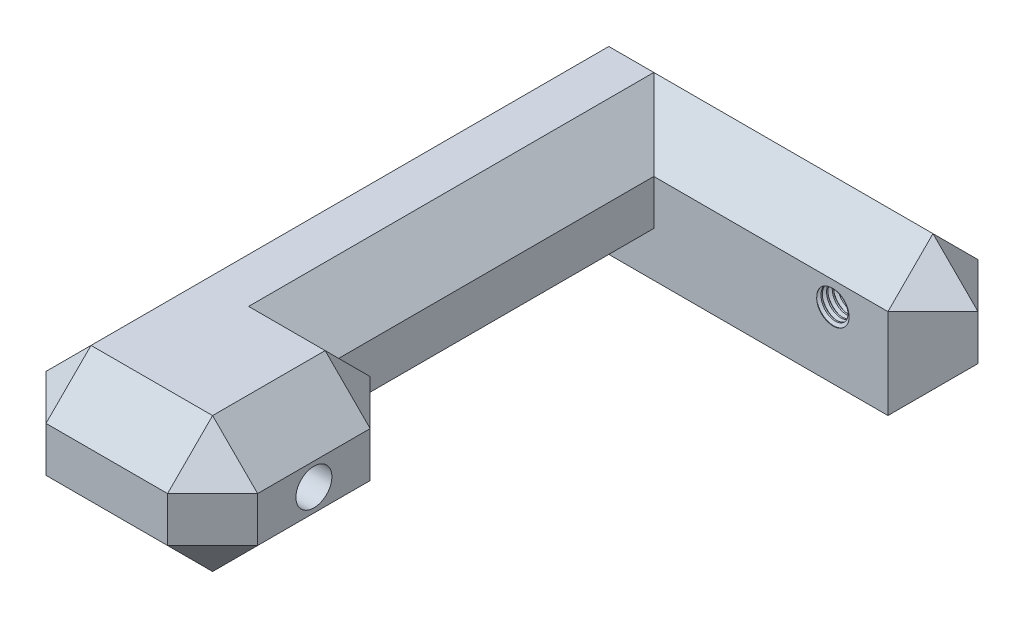
SolidWorks part; units mm, degrees
ref_plane "Front Plane" through (0, 0, 0) normal (0, 0, 1) x (1, 0, 0)
ref_plane "Top Plane" through (0, 0, 0) normal (0, 1, 0) x (1, 0, 0)
ref_plane "Right Plane" through (0, 0, 0) normal (1, 0, 0) x (0, 0, -1)
sketch "Sketch1" plane through (0, 0, 0) normal (0, 1, 0) x (1, 0, 0)
  line L2 (0, 0) -> (0, 45)
  line L3 (0, 45) -> (-17, 45)
  line L5 (0, 0) -> (-47, 0)
  line L6 (-17, 45) -> (-17, 115)
  line L8 (-47, 0) -> (-47, 135)
  line L9 (-47, 135) -> (45, 135)
  line L11 (-17, 115) -> (45, 115)
  line L12 (45, 135) -> (45, 115)
  dimension "D1" = 17
  dimension "D2" = 45
  dimension "D3" = 45
  dimension "D4" = 70
  dimension "D5" = 20
  dimension "D6" = 30
extrude "Main Body" add sketch "Sketch1" along normal mid plane 30
sketch "Sketch3" plane through (-47, 0, 0) normal (-1, 0, 0) x (0, 0, 1)
  line L0 (55, 0) -> (-55, 0) construction
  circle A0 centre (-22.5, 0) radius 7
  dimension "D2" = 14
  dimension "D1" = 22.5
extrude "Cut-Extrude1" cut sketch "Sketch3" against normal blind 40
sketch "Sketch4" plane through (-47, 0, 0) normal (-1, 0, 0) x (0, 0, 1)
  circle A0 centre (-22.5, 0) radius 4
  circle A1 centre (-22.5, 0) radius 7 construction
  dimension "D1" = 8
extrude "Cut-Extrude2" cut sketch "Sketch4" against normal through all
sketch "Sketch6" plane through (0, 0, -135) normal (0, 0, -1) x (-1, 0, 0)
  line L0 (50.6, 0) -> (-50.6, 0) construction
  circle A0 centre (-22.5, 0) radius 3.31
  dimension "D2" = 6.62
  dimension "D1" = 22.5
extrude "Cut-Extrude3" cut sketch "Sketch6" against normal through all
thread "Thread1" pitch 1.25 start angle 0, offset 1.25, length 0, pitch 1.25, diameter 6.62
ref_plane "Plane3" through (19.19, 0, -113.75) normal (0, -1, 0) x (-1, 0, 0)
sketch "Thread Profile3" plane through (19.19, 0, -113.75) normal (0, -1, 0) x (-1, 0, 0)
  line L0 (0, 0) -> (0, 1.25) construction
  line L1 (0, 0) -> (0.6766, 0.3906)
  line L2 (0.6766, 0.3906) -> (0.6766, 0.5469)
  line L3 (0.6766, 0.5469) -> (0, 0.9375)
  line L4 (0.6766, 0.4687) -> (0, 0.4687) construction
  line L11 (0, 0) -> (0, 0.9375)
  point P2 (0, 0)
  dimension "Pitch" = 1.25
  dimension "Profile_Angle" = 60
  dimension "Profile_Land" = 0.1562
  dimension "Profile_Height" = 0.6766
chamfer "Chamfer1" distance 10 angle 45 19 edges at (-47, 15, -67.5) (-1, 15, -135) (14, 15, -115) (-17, 15, -80) (-8.5, 15, -45) (0, 15, -22.5) (-47, 0, 0) (-23.5, 15, 0) (0, 0, 0) (45, 0, -115) (-17, -15, -80) (-8.5, -15, -45) (0, 0, -45) (0, -15, -22.5) (-23.5, -15, 0) (-47, -15, -67.5) (45, 0, -135) (-47, 0, -135) (45, -15, -125)
